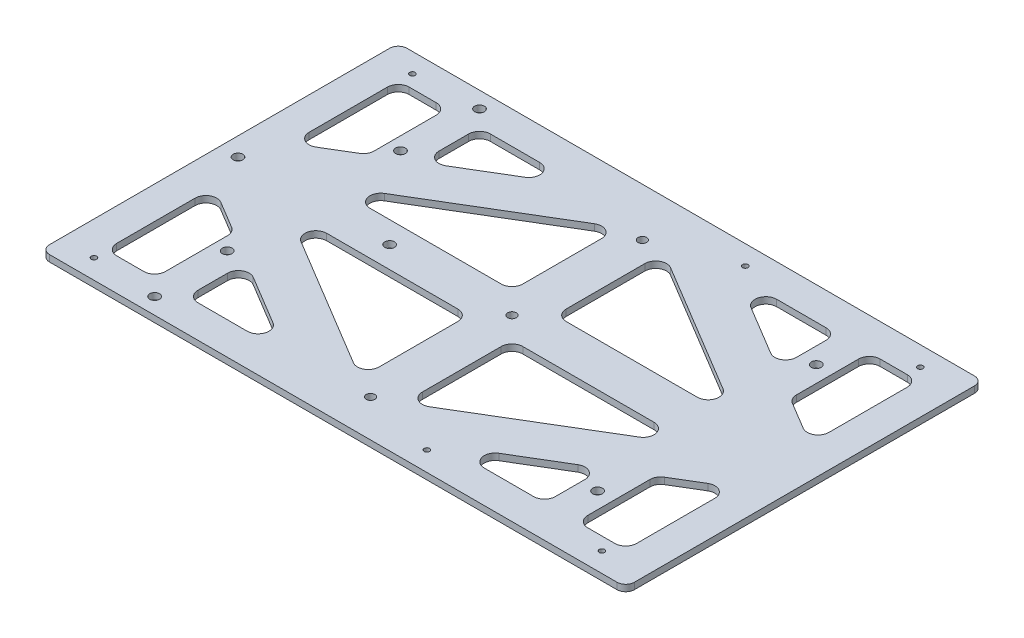
SolidWorks part; units mm, degrees
ref_plane "Alzado" through (0, 0, 0) normal (0, 0, 1) x (1, 0, 0)
ref_plane "Planta" through (0, 0, 0) normal (0, 1, 0) x (1, 0, 0)
ref_plane "Vista lateral" through (0, 0, 0) normal (1, 0, 0) x (0, 0, -1)
sketch "Croquis1" plane through (0, 0, 0) normal (0, 1, 0) x (1, 0, 0)
  line L1 (135, -82.5) -> (-135, -82.5)
  line L2 (135, -82.5) -> (135, 82.5)
  line L3 (135, 82.5) -> (-135, 82.5)
  line L4 (-135, -82.5) -> (-135, 82.5)
  line L5 (135, -82.5) -> (-135, 82.5) construction
  line L6 (135, 82.5) -> (-135, -82.5) construction
  point P0 (0, 0)
  dimension "D1" = 165
  dimension "D2" = 270
extrude "Saliente-Extruir1" add sketch "Croquis1" along normal blind 3
fillet "Redondeo1" radius 4 4 edges at (-135, 1.5, -82.5) (135, 1.5, -82.5) (135, 1.5, 82.5) (-135, 1.5, 82.5)
sketch "Croquis2" plane through (0, 3, 0) normal (0, 1, 0) x (1, 0, 0)
  line L0 (131, 82.5) -> (-131, 82.5) construction
  line L1 (135, -78.5) -> (135, 78.5) construction
  circle A0 centre (90, 50.5) radius 2.25
  dimension "D1" = 4.5
  dimension "D2" = 32
  dimension "D3" = 45
extrude "Cortar-Extruir1" cut sketch "Croquis2" against normal through all
mirror "Simetría1" about plane through (0, 0, 0) normal (0, 0, 1) of "Cortar-Extruir1"
sketch "Croquis3" plane through (0, 3, 0) normal (0, 1, 0) x (1, 0, 0)
  line L0 (-135, 78.5) -> (-135, -78.5) construction
  line L1 (131, 82.5) -> (-131, 82.5) construction
  line L2 (-135, 0) -> (-113.8944, 0) construction
  circle A0 centre (-90, 75) radius 2.25
  circle A1 centre (-90, -75) radius 2.25
  dimension "D1" = 4.5
  dimension "D2" = 45
  dimension "D3" = 7.5
extrude "Cortar-Extruir2" cut sketch "Croquis3" against normal through all
sketch "Croquis4" plane through (0, 3, 0) normal (0, 1, 0) x (1, 0, 0)
  line L0 (0, 82.5) -> (0, -82.5) construction
  line L1 (131, 82.5) -> (-131, 82.5) construction
  line L2 (-131, -82.5) -> (131, -82.5) construction
  line L3 (-135, 0) -> (135, 0) construction
  line L4 (-135, 78.5) -> (-135, -78.5) construction
  line L5 (135, -78.5) -> (135, 78.5) construction
  line L6 (0, -82.5) -> (131, -82.5) construction
  line L7 (135, -82.5) -> (135, 78.5) construction
  line L8 (131, 82.5) -> (0, 82.5) construction
  line L9 (115, 67.5) -> (102.5, 67.5)
  line L12 (110.2817, 0) -> (2.6409, -64.5845) construction
  line L13 (131, 67.5) -> (-131, 67.5) construction
  line L14 (4.9275, 63.2125) -> (110.2817, 0) construction
  line L15 (15, 10) -> (75.5635, 10)
  line L16 (131, 82.5) -> (-131, 82.5) construction
  line L17 (15, -10) -> (75.5635, -10)
  line L18 (10, 51.3381) -> (10, 15)
  line L19 (17.5725, 55.6256) -> (78.136, 19.2875)
  line L20 (78.136, -19.2875) -> (17.5725, -55.6256)
  line L24 (52.1339, 58.2125) -> (74.9275, 44.5363)
  line L29 (15.2174, 80.3624) -> (149.1548, 0) construction
  line L30 (90, 50.5) -> (90, 67.5) construction
  line L31 (149.1548, 0) -> (12.9308, -81.7344) construction
  line L32 (99.9275, 29.5363) -> (112.4275, 22.0363)
  line L34 (82.5, 62.5) -> (82.5, 48.8238)
  line L36 (97.5, 62.5) -> (97.5, 33.8238)
  line L37 (120, 26.3238) -> (120, 62.5)
  line L38 (77.5, 67.5) -> (54.7063, 67.5)
  line L39 (10, -15) -> (10, -51.3381)
  arc A3 (120, 62.5) -> (115, 67.5) centre (115, 62.5) ccw
  arc A4 (120, 26.3238) -> (112.4275, 22.0363) centre (115, 26.3238) cw
  arc A5 (99.9275, 29.5363) -> (97.5, 33.8238) centre (102.5, 33.8238) cw
  arc A6 (102.5, 67.5) -> (97.5, 62.5) centre (102.5, 62.5) ccw
  arc A7 (10, -51.3381) -> (17.5725, -55.6256) centre (15, -51.3381) ccw
  arc A9 (10, 51.3381) -> (17.5725, 55.6256) centre (15, 51.3381) cw
  arc A10 (75.5635, 10) -> (78.136, 19.2875) centre (75.5635, 15) ccw
  arc A11 (75.5635, -10) -> (78.136, -19.2875) centre (75.5635, -15) cw
  arc A12 (15, 10) -> (10, 15) centre (15, 15) cw
  arc A13 (15, -10) -> (10, -15) centre (15, -15) ccw
  arc A14 (82.5, 48.8238) -> (74.9275, 44.5363) centre (77.5, 48.8238) cw
  arc A15 (77.5, 67.5) -> (82.5, 62.5) centre (77.5, 62.5) cw
  arc A16 (52.1339, 58.2125) -> (54.7063, 67.5) centre (54.7063, 62.5) cw
  point P15 (0, 0)
  point P16 (0, 0)
  point P44 (97.5, 30.9929)
  point P64 (10, -10)
  dimension "D5" = 33.6762
  dimension "D6" = 5
  dimension "D7" = 5
  dimension "D13" = 5
  dimension "D14" = 5
  dimension "D15" = 5
  dimension "D16" = 22.0363
  dimension "D2" = 5
  dimension "D4" = 15
  dimension "D8" = 15
  dimension "D10" = 10
  dimension "D11" = 10
  dimension "D12" = 10
  dimension "D3" = 20
  dimension "D1" = 15
extrude "Cortar-Extruir3" cut sketch "Croquis4" against normal through all
mirror "Simetría4" about plane through (0, 0, 0) normal (1, 0, 0) of "Cortar-Extruir3"
sketch "Croquis5" plane through (0, 3, 0) normal (0, 1, 0) x (1, 0, 0)
  line L0 (135, -78.5) -> (135, 78.5) construction
  line L1 (-131, -82.5) -> (131, -82.5) construction
  line L2 (131, 82.5) -> (-131, 82.5) construction
  circle A0 centre (-119.5, 73.5) radius 1.75
  circle A1 centre (34.2, 73.5) radius 1.75
  circle A2 centre (115, 73.5) radius 1.75
  circle A3 centre (115, -73.5) radius 1.75
  circle A4 centre (34.2, -73.5) radius 1.75
  circle A5 centre (-119.5, -73.5) radius 1.75
  point P0 (-119.5, 73.5)
  point P3 (34.2, 73.5)
  point P6 (115, 73.5)
  point P9 (115, -73.5)
  point P12 (34.2, -73.5)
  point P15 (-119.5, -73.5)
  dimension "D1" = 20
  dimension "D2" = 80.8
  dimension "D3" = 153.7
  dimension "D4" = 9
  dimension "D5" = 9
hole_wizard "Taladro roscado M31" positions "Croquis5" profile "Croquis6" tap size "M3" standard "ISO"
sketch "Croquis6" plane through (-119.5, 3, -73.5) normal (1, 0, 0) x (0, 0, 1)
  line L0 (0, 0) -> (0, 9.2511)
  line L1 (0, 9.2511) -> (1.25, 8.5)
  line L2 (1.25, 8.5) -> (1.25, 0)
  line L5 (1.25, 0) -> (0, 0)
  line L10 (0, 9.2511) -> (-1.25, 8.5) construction
  line L11 (0, -6.35) -> (0, 107.95) construction
  dimension "Diámetro de perforador para roscar" = 2.5
  dimension "Profundidad de perforador para roscar" = 8.5
  dimension "Ángulo de perforador" = 118
cosmetic thread "Rosca de taladro1" parameters "D1"=6, "D2"=3
cosmetic thread "Rosca de taladro2" parameters "D1"=6, "D2"=3
cosmetic thread "Rosca de taladro3" parameters "D1"=6, "D2"=3
cosmetic thread "Rosca de taladro4" parameters "D1"=6, "D2"=3
cosmetic thread "Rosca de taladro5" parameters "D1"=6, "D2"=3
cosmetic thread "Rosca de taladro6" parameters "D1"=6, "D2"=3
sketch "Croquis9" plane through (0, 3, 0) normal (0, 1, 0) x (1, 0, 0)
  circle A0 centre (-126.5, 0) radius 2.25
  circle A1 centre (-91.5, 40) radius 2.25
  circle A2 centre (-56.5, 0) radius 2.25
  circle A3 centre (-91.5, -40) radius 2.25
  point P0 (-126.5, 0)
  point P1 (-91.5, -40)
  point P3 (-56.5, 0)
  point P5 (-91.5, 40)
  dimension "D1" = 4.5
extrude "Cortar-Extruir4" cut sketch "Croquis9" against normal blind 4
mirror "Simetría5" about plane through (0, 0, 0) normal (0, 0, 1) of face at (97.5, 1.5, -48.1619) of face at (98.4314, 1.5, -31.5202) of face at (106.1775, 1.5, -25.7863) of face at (116.8386, 1.5, -23.0764) of face at (120, 1.5, -44.4119) of face at (118.0178, 1.5, -65.5178) of face at (108.75, 1.5, -67.5) of face at (99.4822, 1.5, -65.5178) of face at (63.5307, 1.5, -51.3744) of face at (79.3386, 1.5, -45.5764) of face at (82.5, 1.5, -55.6619) of face at (80.5178, 1.5, -65.5178) of face at (66.1032, 1.5, -67.5) of face at (51.6539, 1.5, -63.3455)
mirror "Simetría7" about plane through (0, 0, 0) normal (1, 0, 0) of face at (80.5178, 1.5, 65.5178) of face at (66.1032, 1.5, 67.5) of face at (51.6539, 1.5, 63.3455) of face at (82.5, 1.5, 55.6619) of face at (79.3386, 1.5, 45.5764) of face at (63.5307, 1.5, 51.3744)
mirror "Simetría8" about plane through (0, 0, 0) normal (1, 0, 0) of face at (106.1775, 1.5, 25.7863) of face at (116.8386, 1.5, 23.0764) of face at (120, 1.5, 44.4119) of face at (118.0178, 1.5, 65.5178) of face at (108.75, 1.5, 67.5) of face at (99.4822, 1.5, 65.5178) of face at (98.4314, 1.5, 31.5202) of face at (97.5, 1.5, 48.1619)
sketch "Croquis10" plane through (0, 3, 0) normal (0, 1, 0) x (1, 0, 0)
  circle A0 centre (0, 0) radius 2
  circle A1 centre (0, 60.1959) radius 2
  circle A2 centre (0, -65.3126) radius 2
  dimension "D1" = 4
extrude "Cortar-Extruir5" cut sketch "Croquis10" against normal through all
